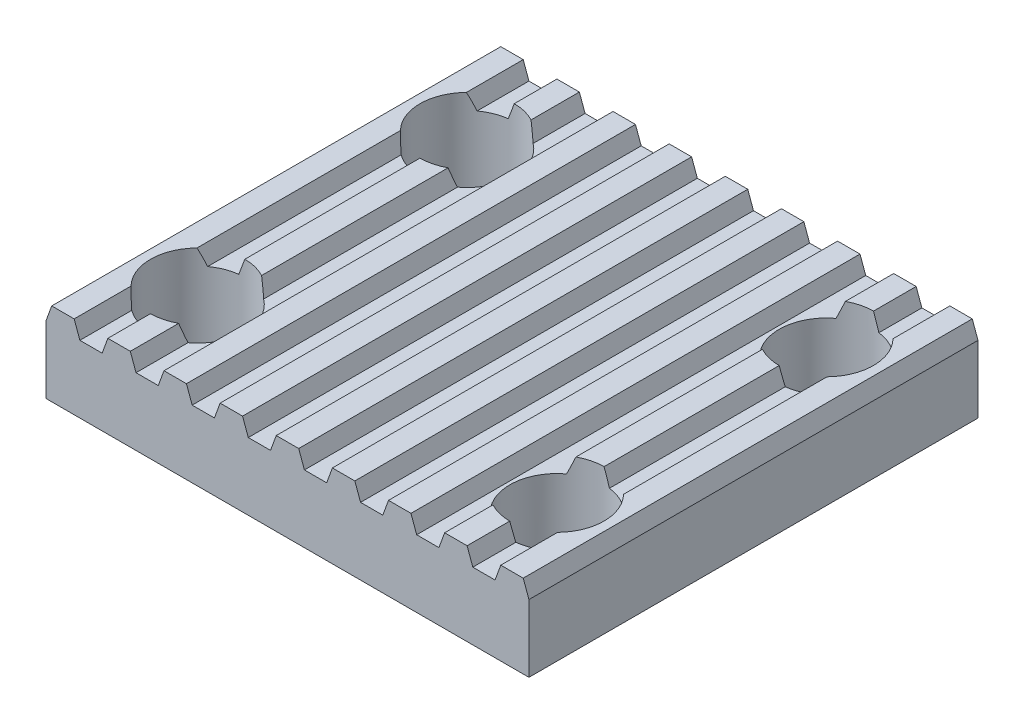
SolidWorks part; units mm, degrees
ref_plane "Front Plane" through (0, 0, 0) normal (0, 0, 1) x (1, 0, 0)
ref_plane "Top Plane" through (0, 0, 0) normal (0, 1, 0) x (1, 0, 0)
ref_plane "Right Plane" through (0, 0, 0) normal (1, 0, 0) x (0, 0, -1)
sketch "Sketch1" plane through (0, 0, 0) normal (0, 0, 1) x (1, 0, 0)
  line L0 (-10.7548, 1.5) -> (-10.5, 2.2)
  line L1 (10.7548, -1.5) -> (-10.7548, -1.5)
  line L4 (-10.7548, -1.5) -> (-10.7548, 1.5)
  line L5 (-10.7548, 1.5) -> (10.7548, -1.5) construction
  line L6 (10.7548, 1.5) -> (-10.7548, -1.5) construction
  line L7 (-10.5, 2.2) -> (-9.5, 2.2)
  line L8 (-9.5, 2.2) -> (-9.2452, 1.5)
  line L9 (-10.7548, 1.5) -> (-9.2452, 1.5) construction
  line L13 (-10, 1.5) -> (-10, 2.2) construction
  line L32 (10.7548, 1.5) -> (10.7548, -1.5)
  line L33 (-8, 2.2) -> (-7, 2.2)
  line L34 (-8.2548, 1.5) -> (-8, 2.2)
  line L35 (-7, 2.2) -> (-6.7452, 1.5)
  line L36 (-5.5, 2.2) -> (-4.5, 2.2)
  line L37 (-5.7548, 1.5) -> (-5.5, 2.2)
  line L38 (-4.5, 2.2) -> (-4.2452, 1.5)
  line L39 (-3, 2.2) -> (-2, 2.2)
  line L40 (-3.2548, 1.5) -> (-3, 2.2)
  line L41 (-2, 2.2) -> (-1.7452, 1.5)
  line L42 (-0.5, 2.2) -> (0.5, 2.2)
  line L43 (-0.7548, 1.5) -> (-0.5, 2.2)
  line L44 (0.5, 2.2) -> (0.7548, 1.5)
  line L45 (2, 2.2) -> (3, 2.2)
  line L46 (1.7452, 1.5) -> (2, 2.2)
  line L47 (3, 2.2) -> (3.2548, 1.5)
  line L48 (4.5, 2.2) -> (5.5, 2.2)
  line L49 (4.2452, 1.5) -> (4.5, 2.2)
  line L50 (5.5, 2.2) -> (5.7548, 1.5)
  line L51 (7, 2.2) -> (8, 2.2)
  line L52 (6.7452, 1.5) -> (7, 2.2)
  line L53 (8, 2.2) -> (8.2548, 1.5)
  line L54 (9.5, 2.2) -> (10.5, 2.2)
  line L55 (9.2452, 1.5) -> (9.5, 2.2)
  line L56 (10.5, 2.2) -> (10.7548, 1.5)
  line L60 (-9.2452, 1.5) -> (-8.2548, 1.5)
  line L61 (-6.7452, 1.5) -> (-5.7548, 1.5)
  line L62 (-4.2452, 1.5) -> (-3.2548, 1.5)
  line L63 (-1.7452, 1.5) -> (-0.7548, 1.5)
  line L64 (0.7548, 1.5) -> (1.7452, 1.5)
  line L65 (3.2548, 1.5) -> (4.2452, 1.5)
  line L66 (5.7548, 1.5) -> (6.7452, 1.5)
  line L67 (8.2548, 1.5) -> (9.2452, 1.5)
  line L70 (13.2548, 1.5) -> (14.2452, 1.5) [skipped]
  line L71 (11.7452, 1.5) -> (12, 2.2) [skipped]
  line L72 (12, 2.2) -> (13, 2.2) [skipped]
  line L73 (13, 2.2) -> (13.2548, 1.5) [skipped]
  line L74 (10.7548, 1.5) -> (11.7452, 1.5) [skipped]
  point P0 (0, 0)
  point P2 (0, 0)
  point P3 (0, 0)
  point P11 (0, 0)
  dimension "D1" = 3
  dimension "D2" = 3.7
  dimension "D3" = 40
  dimension "D4" = 1
  dimension "D5" = 10
  dimension "D6" = 10
extrude "Boss-Extrude1" add sketch "Sketch1" along normal mid plane 20
sketch "Sketch2" plane through (0, -1.5, 0) normal (0, -1, 0) x (1, 0, 0)
  line L0 (-11.516, 0) -> (10.7548, 0) construction
  line L1 (2.035, 0) -> (-2.035, 0) construction
  line L2 (10.7548, 10) -> (10.7548, -10) construction
  line L3 (0, 10) -> (0, -10) construction
  line L4 (-10.7548, 10) -> (10.7548, 10) construction
  line L5 (-10.7548, -10) -> (10.7548, -10) construction
  circle A0 centre (-8, -6) radius 2.1
  circle A1 centre (8, -6) radius 2.1
  circle A2 centre (8, 6) radius 2.1
  circle A3 centre (-8, 6) radius 2.1
  dimension "D1" = 16
  dimension "D2" = 12
  dimension "D3" = 4.2
extrude "Cut-Extrude1" cut sketch "Sketch2" against normal through all
